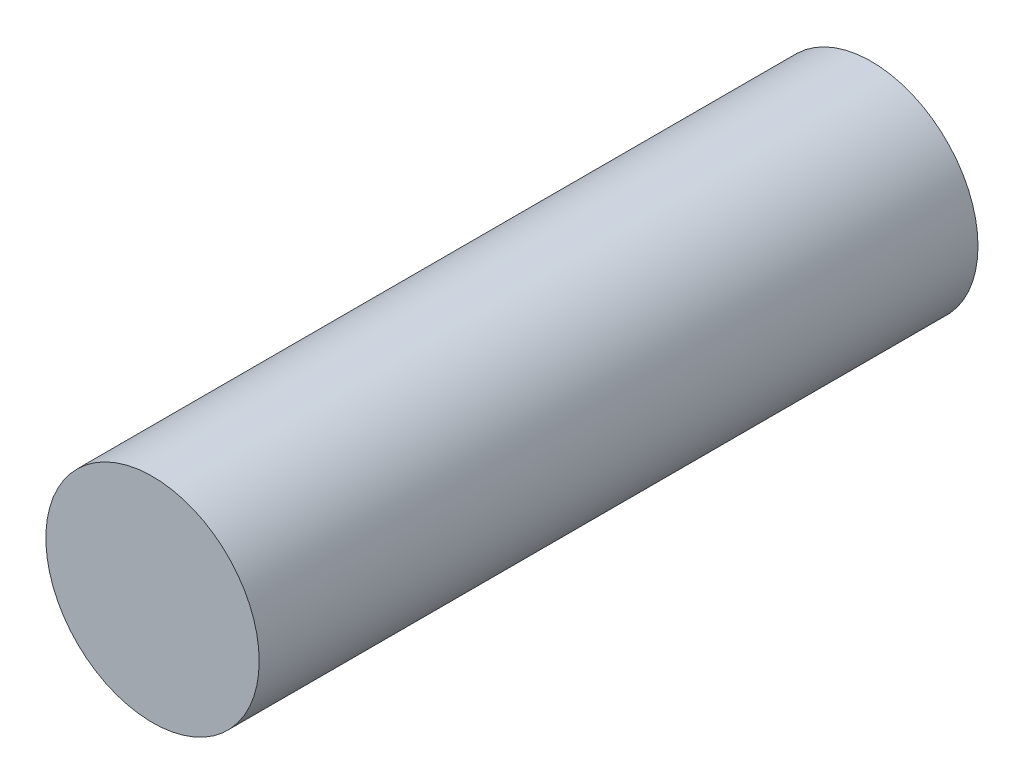
SolidWorks part; units mm, degrees
ref_plane "Front Plane" through (0, 0, 0) normal (0, 0, 1) x (1, 0, 0)
ref_plane "Top Plane" through (0, 0, 0) normal (0, 1, 0) x (1, 0, 0)
ref_plane "Right Plane" through (0, 0, 0) normal (1, 0, 0) x (0, 0, -1)
sketch "Sketch1" plane through (0, 0, 0) normal (0, 0, 1) x (1, 0, 0)
  circle A0 centre (0, 0) radius 2.3
  dimension "D1" = 4.6
extrude "Boss-Extrude1" add sketch "Sketch1" along normal blind 15.5
